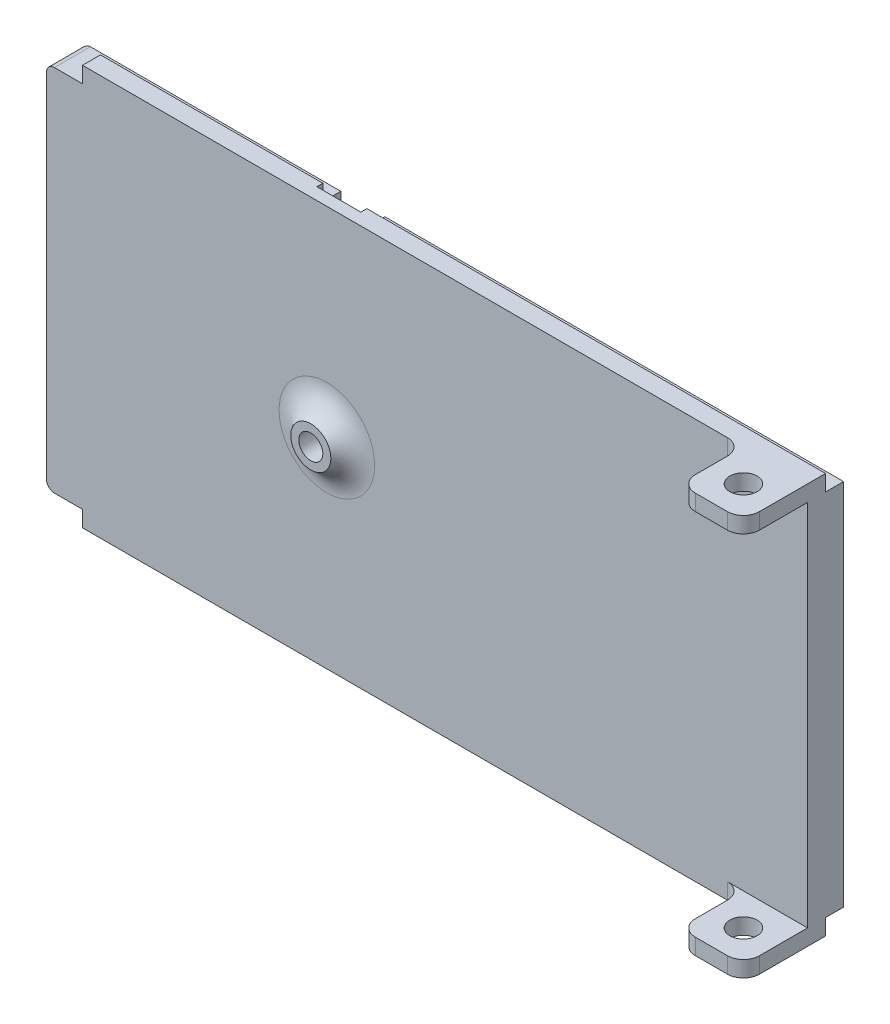
SolidWorks part; units mm, degrees
ref_plane "Front Plane" through (0, 0, 0) normal (1, 0, 0) x (0, 1, 0)
ref_plane "Top Plane" through (0, 0, 0) normal (0, 0, 1) x (0, 1, 0)
ref_plane "Right Plane" through (0, 0, 0) normal (0, 1, 0) x (-1, 0, 0)
sketch "Sketch1" plane through (0, 0, 0) normal (0, 0, 1) x (0, 1, 0)
  line L1 (0, 0) -> (50, 0)
  line L2 (0, 0) -> (0, 95)
  line L3 (0, 95) -> (50, 95)
  line L4 (50, 0) -> (50, 95)
  dimension "D1" = 50
  dimension "D2" = 95
extrude "Boss-Extrude1" add sketch "Sketch1" along normal blind 4.5 contours L3 L4 L1 L2
sketch "Sketch2" plane through (0, 0, 4.5) normal (0, 0, 1) x (1, 0, 0)
  line L0 (-95, 25) -> (0, 25) construction
  line L1 (-95, 0) -> (-95, 50) construction
  line L2 (0, 0) -> (0, 50) construction
  circle A0 centre (-60, 25) radius 0.5
  dimension "D1" = 1
  dimension "D2" = 35
extrude "Cut-Extrude1" cut sketch "Sketch2" against normal through all
sketch "Sketch3" plane through (-95, 0, 0) normal (-1, 0, 0) x (0, -1, 0)
  line L0 (-25, 4.5) -> (-25, 0) construction
  line L1 (0, 4.5) -> (-50, 4.5) construction
  line L2 (0, 0) -> (-50, 0) construction
  line L4 (-50, 2.25) -> (-48, 2.25)
  line L5 (-50, 2.25) -> (-50, 0)
  line L6 (-50, 0) -> (-48, 0)
  line L7 (-48, 2.25) -> (-48, 0)
  line L8 (0, 0) -> (-2, 0)
  line L9 (-2, 2.25) -> (-2, 0)
  line L10 (0, 2.25) -> (-2, 2.25)
  line L11 (0, 2.25) -> (0, 0)
  line L12 (-50, 4.5) -> (-50, 0) construction
  line L13 (0, 4.5) -> (0, 0) construction
  dimension "D1" = 2
extrude "Cut-Extrude2" cut sketch "Sketch3" against normal through all
sketch "Sketch5" plane through (0, 0, 4.5) normal (0, 0, 1) x (1, 0, 0)
  circle A0 centre (-60, 25) radius 2.5
  dimension "D1" = 5
extrude "Boss-Extrude2" add sketch "Sketch5" along normal blind 2
sketch "Sketch6" plane through (0, 0, 6.5) normal (0, 0, 1) x (1, 0, 0)
  circle A0 centre (-60, 25) radius 1.5
  dimension "D1" = 3
extrude "Cut-Extrude3" cut sketch "Sketch6" against normal through all
fillet "Fillet1" radius 4 1 edges at (-62.5, 25, 4.5)
sketch "Sketch8" plane through (0, 0, 0) normal (0, 0, -1) x (1, 0, 0)
  line L0 (0, -50) -> (-95, -50) construction
  line L1 (-62.75, -50) -> (-57.25, -50)
  line L2 (-62.75, -50) -> (-62.75, -20)
  line L3 (-62.75, -20) -> (-57.25, -20)
  line L4 (-57.25, -50) -> (-57.25, -20)
  line L5 (-60, -25) -> (-60, -20) construction
  dimension "D1" = 5.5
  dimension "D2" = 30
extrude "Cut-Extrude4" cut sketch "Sketch8" against normal blind 3
sketch "Sketch10" plane through (-95, 0, 0) normal (-1, 0, 0) x (0, -1, 0)
  line L1 (-48, 2.25) -> (-50, 2.25)
  line L2 (-48, 2.25) -> (-48, 4.5)
  line L3 (-48, 4.5) -> (-50, 4.5)
  line L4 (-50, 2.25) -> (-50, 4.5)
  line L5 (-2, 2.25) -> (0, 2.25)
  line L6 (-2, 2.25) -> (-2, 4.5)
  line L7 (-2, 4.5) -> (0, 4.5)
  line L8 (0, 2.25) -> (0, 4.5)
extrude "Cut-Extrude5" cut sketch "Sketch10" against normal blind 4.5
fillet "Fillet2" radius 1 3 edges at (-95, 2, 2.25) (-95, 25, 0) (-95, 48, 2.25)
sketch "Sketch11" plane through (0, 0, 4.5) normal (0, 0, 1) x (1, 0, 0)
  line L0 (0, 25) -> (-57.5, 25) construction
  line L1 (0, 50) -> (-8, 50)
  line L2 (0, 50) -> (0, 48)
  line L3 (0, 48) -> (-8, 48)
  line L4 (-8, 50) -> (-8, 48)
  line L5 (0, 0) -> (0, 50) construction
  line L6 (0, 2) -> (-8, 2)
  line L7 (-8, 0) -> (-8, 2)
  line L8 (0, 0) -> (-8, 0)
  line L9 (0, 0) -> (0, 2)
  circle A0 centre (-60, 25) radius 2.5 construction
  dimension "D1" = 2
  dimension "D2" = 8
extrude "Boss-Extrude3" add sketch "Sketch11" along normal blind 8
sketch "Sketch12" plane through (0, 50, 0) normal (0, 1, 0) x (-1, 0, 0)
  line L0 (4, 12.5) -> (4, 2.25) construction
  line L1 (0, 12.5) -> (8, 12.5) construction
  line L2 (0, 2.25) -> (57.25, 2.25) construction
  line L3 (8, 8.5) -> (0, 8.5) construction
  line L4 (8, 12.5) -> (8, 4.5) construction
  line L5 (0, 12.5) -> (0, 2.25) construction
  circle A0 centre (4, 8.5) radius 1.7
  dimension "D1" = 3.4
extrude "Cut-Extrude6" cut sketch "Sketch12" against normal through all both and the other way through all
fillet "Fillet3" radius 2 6 edges at (0, 1, 12.5) (-8, 1, 12.5) (-8, 1, 4.5) (-8, 49, 4.5) (-8, 49, 12.5) (0, 49, 12.5)
